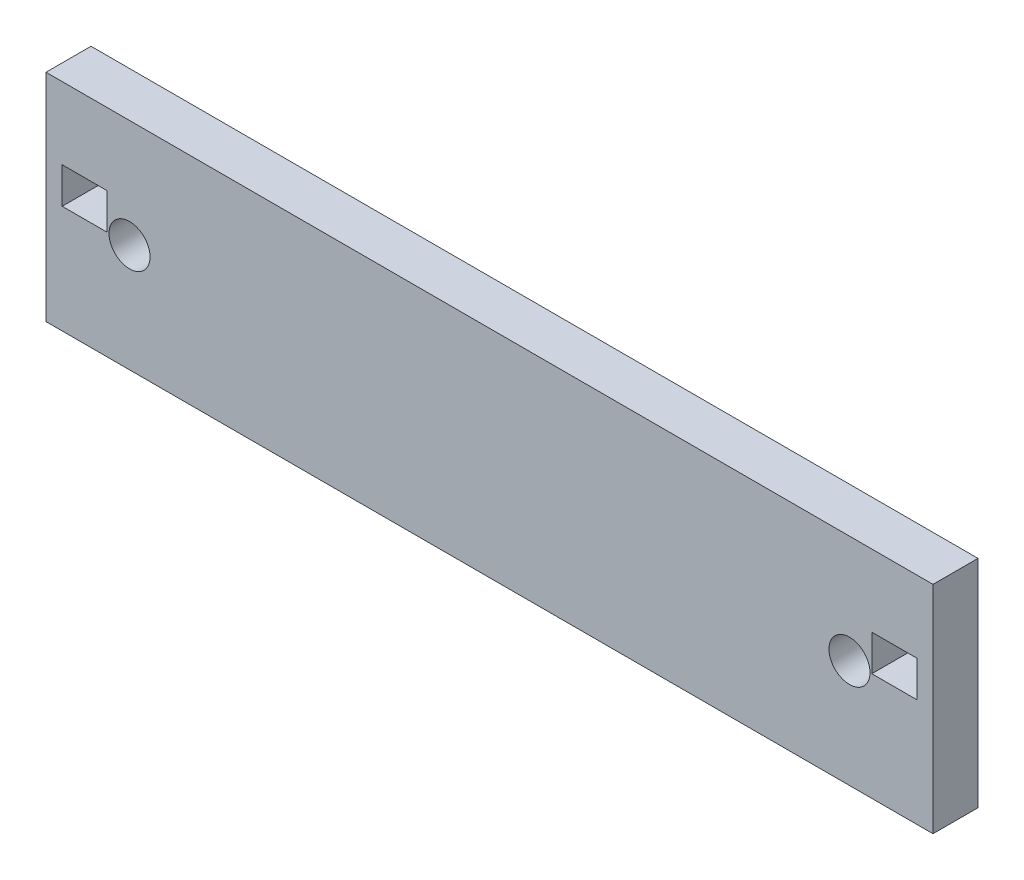
SolidWorks part; units mm, degrees
material "Beech"
ref_plane "Front Plane" through (0, 0, 0) normal (0, 0, 1) x (1, 0, 0)
ref_plane "Top Plane" through (0, 0, 0) normal (0, 1, 0) x (1, 0, 0)
ref_plane "Right Plane" through (0, 0, 0) normal (1, 0, 0) x (0, 0, -1)
sketch "Sketch1" plane through (0, 0, 0) normal (0, 0, 1) x (1, 0, 0)
  line L0 (0, -1000) -> (0, 49000) construction
  line L1 (-18.034, -3.81) -> (13.2588, -3.81)
  line L2 (-18.034, -3.81) -> (-18.034, 3.81)
  line L3 (-18.034, 3.81) -> (13.2588, 3.81)
  line L4 (13.2588, -3.81) -> (13.2588, 3.81)
  line L5 (12.6873, 1.27) -> (13.2588, 1.27) construction
  line L6 (10.3124, -3.81) -> (10.3124, 0) construction
  line L7 (-17.4625, 0) -> (-15.875, 0)
  line L8 (-17.4625, 0) -> (-17.4625, 1.27)
  line L9 (-17.4625, 1.27) -> (-15.875, 1.27)
  line L10 (-15.875, 0) -> (-15.875, 1.27)
  line L11 (11.0998, 0) -> (11.0998, 1.27)
  line L12 (12.6873, 1.27) -> (11.0998, 1.27)
  line L13 (12.6873, 0) -> (12.6873, 1.27)
  line L14 (12.6873, 0) -> (11.0998, 0)
  line L15 (-1000, 0) -> (49000, 0) construction
  line L16 (10.3124, 0) -> (10.3124, 3.81) construction
  line L17 (-17.4625, 1.27) -> (-18.034, 1.27) construction
  circle A0 centre (-15.0876, 0) radius 0.7239
  circle A1 centre (10.3124, 0) radius 0.7239
  point P0 (0, 0)
  dimension "D6" = 1.4478
  dimension "D7" = 0.7874
  dimension "D1" = 0.5715
  dimension "D2" = 7.62
  dimension "D3" = 1.5875
  dimension "D4" = 15.875
  dimension "D5" = 1.27
  dimension "D8" = 0.7874
  dimension "D9" = 25.4
extrude "Boss-Extrude1" add sketch "Sketch1" along normal blind 1.5875
